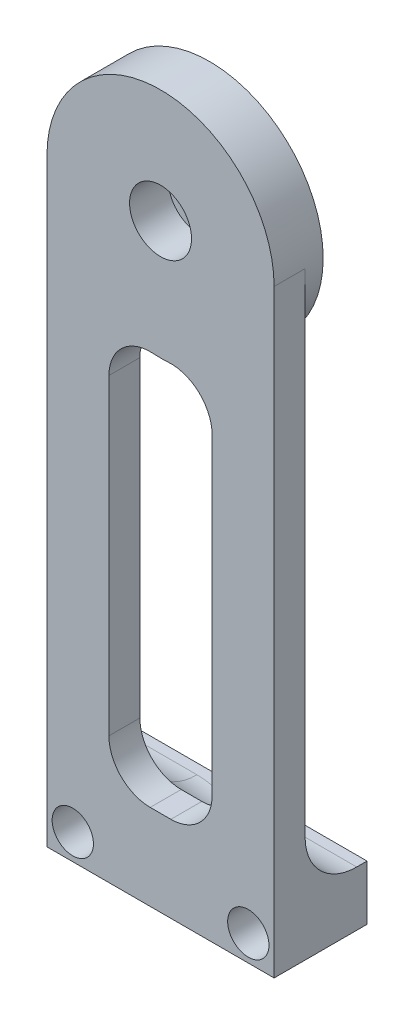
SolidWorks part; units mm, degrees
ref_plane "Front Plane" through (0, 0, 0) normal (0, 0, 1) x (1, 0, 0)
ref_plane "Top Plane" through (0, 0, 0) normal (0, 1, 0) x (1, 0, 0)
ref_plane "Right Plane" through (0, 0, 0) normal (1, 0, 0) x (0, 0, -1)
sketch "Sketch1" plane through (0, 0, 0) normal (0, 0, 1) x (1, 0, 0)
  line L0 (0, 29) -> (0, -29) construction
  line L1 (-11, 29) -> (-11, -29)
  line L2 (11, 29) -> (11, -29)
  line L3 (-11, -29) -> (11, -29)
  line L5 (-11, -29) -> (11, -29)
  line L6 (-11, -29) -> (-11, -23.69)
  line L7 (-11, -23.69) -> (11, -23.69)
  line L8 (11, -29) -> (11, -23.69)
  line L10 (-5, 18.6438) -> (-5, -20.69)
  line L11 (-5, -20.69) -> (5, -20.69)
  line L12 (5, 18.6438) -> (5, -20.69)
  circle A0 centre (0, 29) radius 11
  arc A2 (-5, 18.6438) -> (5, 18.6438) centre (0, 29) ccw
  point P8 (0, 0)
  dimension "D2" = 22
  dimension "D6" = 6
  dimension "D7" = 11.5
  dimension "D1" = 58
  dimension "D3" = 5.31
  dimension "D4" = 3
  dimension "D5" = 6
extrude "Boss-Extrude1" add sketch "Sketch1" along normal blind 3 contours A0 | L0 A0 L1 | A0 L0 L2 | L6 L5 L8 L7 region at (7.7455, -1.7215, 0) region at (-7.7455, -1.7215, 0) region at (-7.5582, 21.4418, 0)
extrude "Boss-Extrude2" add sketch "Sketch1<3>" against normal blind 1.75 contours A0 region at (0, 29, 0)
sketch "Sketch1<3>" plane through (0, 0, 0) normal (0, 0, 1) x (1, 0, 0) same geometry as "Sketch1"
sketch "Sketch2" plane through (0, 0, 3) normal (0, 0, 1) x (1, 0, 0)
  circle A0 centre (0, 29) radius 1.75
  circle A3 centre (0, 29) radius 3
  dimension "D1" = 3.5
  dimension "D2" = 6
extrude "Cut-Extrude1" cut sketch "Sketch2" against normal up to surface (4.75 mm away) contours A0 region at (0, 29, 3) up to face at (11, 29, -1.75)
extrude "Cut-Extrude2" cut sketch "Sketch2<3>" against normal offset from surface (3.75 mm away) 1 contours A3 A0 region at (-2.9151, 29, 3) up to face at (1.75, 29, -1.75)
sketch "Sketch2<3>" plane through (0, 0, 3) normal (0, 0, 1) x (1, 0, 0) same geometry as "Sketch2"
extrude "Boss-Extrude3" add sketch "Sketch1<6>" against normal blind 6 contours L7 L0 L5 L2 | L0 L7 L1 L3 region at (-5.5, -26.345, 0) region at (5.5, -26.345, 0)
sketch "Sketch1<6>" plane through (0, 0, 0) normal (0, 0, 1) x (1, 0, 0) same geometry as "Sketch1"
sketch "Sketch3" plane through (0, 0, 3) normal (0, 0, 1) x (1, 0, 0)
  line L1 (-8.5, -26.505) -> (8.5, -26.505) construction
  line L2 (-11, -29) -> (11, -29) construction
  circle A1 centre (-8.5, -26.505) radius 1.1
  circle A2 centre (8.5, -26.505) radius 1.1
  circle A3 centre (-8.5, -26.505) radius 2
  circle A4 centre (8.5, -26.505) radius 2
  point P5 (0, -26.505)
  dimension "D2" = 2.2
  dimension "D3" = 4
  dimension "D4" = 2.495
  dimension "D1" = 17
extrude "Cut-Extrude3" cut sketch "Sketch3" against normal up to surface (9 mm away) contours A1 | A2 region at (-8.5, -26.505, 3) up to face at (0, -26.345, -6)
extrude "Cut-Extrude4" cut sketch "Sketch3<3>" against normal offset from surface (8 mm away) 1 up to face at (-7.4, -26.505, -6)
sketch "Sketch3<3>" plane through (0, 0, 3) normal (0, 0, 1) x (1, 0, 0) same geometry as "Sketch3"
fillet "Filete1" radius 4 4 edges at (5, 18.6438, 1.5) (-5, 18.6438, 1.5) (5, -20.69, 1.5) (-5, -20.69, 1.5)
fillet "Filete2" radius 5 1 edges at (0, -23.69, 0)
move or copy body "Corpo-Mover/Copiar1" [suppressed] bodies to move or copy 118
